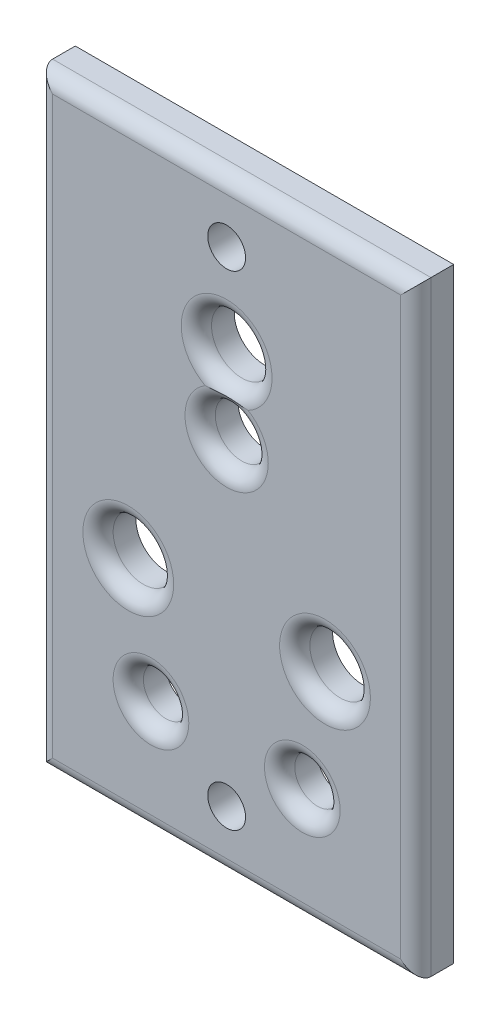
SolidWorks part; units mm, degrees
ref_plane "Front Plane" through (0, 0, 0) normal (0, 0, 1) x (1, 0, 0)
ref_plane "Top Plane" through (0, 0, 0) normal (0, 1, 0) x (1, 0, 0)
ref_plane "Right Plane" through (0, 0, 0) normal (1, 0, 0) x (0, 0, -1)
sketch "Sketch1" plane through (0, 0, 0) normal (0, 0, 1) x (1, 0, 0)
  line L0 (25, 40) -> (-25, -40) construction
  line L1 (-25, 40) -> (25, 40)
  line L2 (-25, 40) -> (-25, -40)
  line L3 (-25, -40) -> (25, -40)
  line L4 (25, 40) -> (25, -40)
  dimension "D1" = 50
  dimension "D2" = 80
extrude "Extrude1" add sketch "Sketch1" along normal blind 5
sketch "Sketch2" plane through (0, 0, 5) normal (0, 0, 1) x (1, 0, 0)
  line L0 (0, 40) -> (0, -40) construction
  line L1 (25, 40) -> (-25, 40) construction
  line L2 (-25, -40) -> (25, -40) construction
  circle A0 centre (-10, -25) radius 3
  circle A1 centre (10, -25) radius 3
  circle A2 centre (0, 20) radius 4
  circle A3 centre (13, -10.1124) radius 4
  circle A4 centre (-13, -10.1124) radius 4
  circle A5 centre (0, 10) radius 3.5
  dimension "D1" = 6
  dimension "D2" = 10
  dimension "D3" = 10
  dimension "D4" = 15
  dimension "D5" = 15
  dimension "D6" = 20
  dimension "D7" = 8
  dimension "D8" = 8
  dimension "D9" = 7
  dimension "D10" = 30
  dimension "D11" = 13
  dimension "D12" = 13
extrude "Cut-Extrude1" cut sketch "Sketch2" against normal through all
fillet "Fillet1" radius 2 10 edges at (0, 40, 5) (25, 0, 5) (0, -40, 5) (-25, 0, 5) (-7, -25, 5) (13, -25, 5) (4, 20, 5) (17, -10.1124, 5) (-9, -10.1124, 5) (3.5, 10, 5)
sketch "Sketch5" plane through (0, 0, 5) normal (0, 0, 1) x (1, 0, 0)
  line L0 (0, 40) -> (0, -40) construction
  line L1 (-25, 40) -> (25, 40) construction
  line L2 (25, -40) -> (-25, -40) construction
  circle A0 centre (0, 32) radius 2.5
  circle A1 centre (0, -32) radius 2.5
  dimension "D1" = 5
  dimension "D2" = 32
  dimension "D3" = 32
extrude "Cut-Extrude2" cut sketch "Sketch5" against normal blind 10
